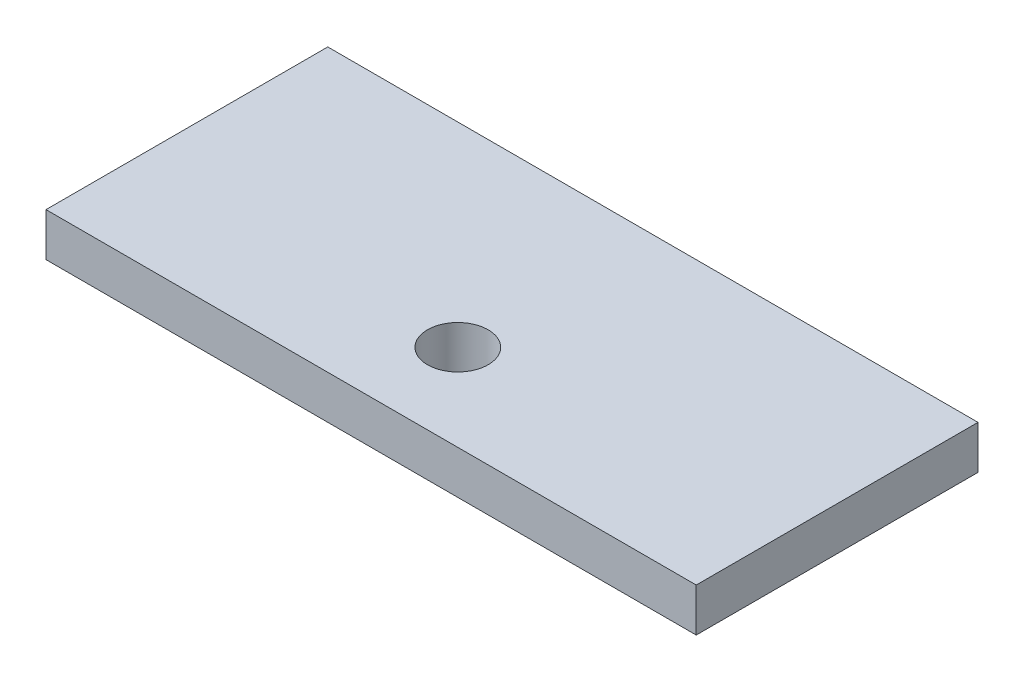
SolidWorks part; units mm, degrees
ref_plane "Front Plane" through (0, 0, 0) normal (0, 0, 1) x (1, 0, 0)
ref_plane "Top Plane" through (0, 0, 0) normal (0, 1, 0) x (1, 0, 0)
ref_plane "Right Plane" through (0, 0, 0) normal (1, 0, 0) x (0, 0, -1)
sketch "Sketch1" plane through (0, 0, 0) normal (0, 1, 0) x (1, 0, 0)
  line L1 (-75, -32.5) -> (75, -32.5)
  line L2 (-75, -32.5) -> (-75, 32.5)
  line L3 (-75, 32.5) -> (75, 32.5)
  line L4 (75, -32.5) -> (75, 32.5)
  line L5 (-75, -32.5) -> (75, 32.5) construction
  line L6 (-75, 32.5) -> (75, -32.5) construction
  point P0 (0, 0)
  dimension "D1" = 150
  dimension "D2" = 65
extrude "Boss-Extrude1" add sketch "Sketch1" along normal blind 10
sketch "Sketch2" plane through (0, 0, 0) normal (0, 1, 0) x (1, 0, 0)
  line L0 (0, -12.5) -> (0, 781.074) construction
  line L1 (-75, -32.5) -> (75, -32.5) construction
  circle A0 centre (0, -12.5) radius 7
  dimension "D1" = 14
  dimension "D2" = 20
extrude "Cut-Extrude2" cut sketch "Sketch2" against normal through all and the other way through all
